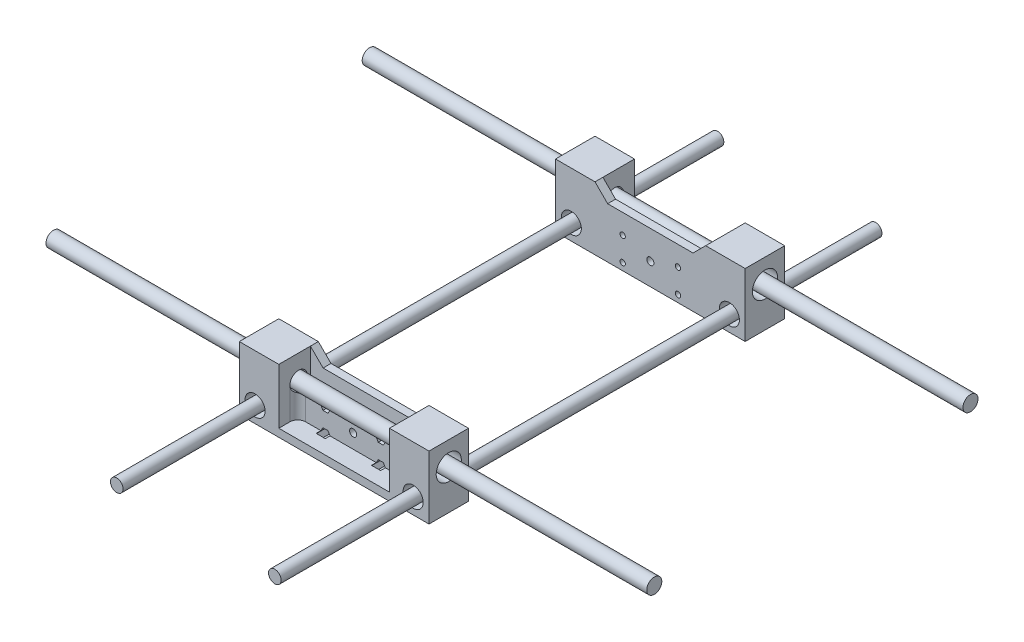
SolidWorks part; units mm, degrees
note: The reader was unsure of these and kept them because the rebuilt part matched: shared geometry of "Sketch3<3>".
ref_plane "Front" through (0, 0, 0) normal (0, 0, 1) x (1, 0, 0)
ref_plane "Top" through (0, 0, 0) normal (0, 1, 0) x (1, 0, 0)
ref_plane "Right" through (0, 0, 0) normal (1, 0, 0) x (0, 0, -1)
sketch "Sketch1" plane through (0, 0, 0) normal (0, 0, 1) x (1, 0, 0)
  line L0 (-50, 0) -> (50, 0) construction
  line L1 (0, 0) -> (0, 10) construction
  line L2 (35, 10) -> (-35, 10)
  line L3 (60, 30) -> (60, -10)
  line L4 (60, -10) -> (-60, -10)
  line L5 (-60, 30) -> (-60, -10)
  line L7 (-60, 30) -> (-35, 30)
  line L8 (-35, 30) -> (-35, 10)
  line L9 (35, 10) -> (35, 30)
  line L10 (35, 30) -> (60, 30)
  circle A0 centre (50, 0) radius 6.35
  circle A1 centre (-50, 0) radius 6.35
  dimension "Sleeve Bearing OD" = 12.7
  dimension "D1" = 100
  dimension "D3" = 120
  dimension "D4" = 20
  dimension "D5" = 20
  dimension "D6" = 25
extrude "Boss-Extrude1" add sketch "Sketch1" along normal mid plane 25
sketch "Sketch3" plane through (-60, 0, 0) normal (-1, 0, 0) x (0, 0, 1)
  line L0 (0, 0) -> (0, 15) construction
  circle A0 centre (0, 15) radius 7.9375
  circle A1 centre (0, 15) radius 5.5
  dimension "D1" = 15.875
  dimension "Sliding Shaft Clearance Hole" = 11
  dimension "D2" = 15
extrude "Cut-Extrude1" cut sketch "Sketch3" against normal blind 12
extrude "Cut-Extrude3" cut sketch "Sketch3<3>" against normal up to surface (95 mm away) contours A1
sketch "Sketch3<3>" plane through (-60, 0, 0) normal (-1, 0, 0) x (0, 0, 1) same geometry as "Sketch3"
mirror "Mirror1" about plane through (0, 0, 0) normal (1, 0, 0) of "Cut-Extrude3", "Cut-Extrude1"
sketch "Sketch4" plane through (0, 0, -12.5) normal (0, 0, -1) x (-1, 0, 0)
  line L0 (60, -10) -> (-60, -10) construction
  line L1 (-35, 10) -> (35, 10)
  line L2 (-35, 10) -> (-35, -10)
  line L3 (-35, -10) -> (35, -10)
  line L4 (35, 10) -> (35, -10)
  line L5 (35, 10) -> (35, 30) construction
  line L6 (-35, 10) -> (35, 10) construction
extrude "Cut-Extrude2" cut sketch "Sketch4" against normal blind 12
sketch "Sketch8" plane through (0, 0, 12.5) normal (0, 0, -1) x (-1, 0, 0)
  line L0 (35, 30) -> (60, 30) construction
  line L1 (-35, 30) -> (-35, -10) construction
  line L2 (-35, 30) -> (-35, -10)
  line L4 (35, -10) -> (35, 30) construction
  line L5 (-35, -10) -> (35, -10)
  line L6 (35, -10) -> (35, 30)
  line L7 (-35, 30) -> (-27, 22)
  line L8 (-27, 22) -> (27, 22)
  line L9 (27, 22) -> (35, 30)
  line L10 (0, 0) -> (0, 22) construction
  line L11 (35, 10) -> (-35, 10) construction
  dimension "D1" = 12
  dimension "D2" = 45
  dimension "D3" = 8
extrude "Boss-Extrude5" add sketch "Sketch8" along normal blind 5
fillet "Fillet4" [suppressed] radius 15
sketch "Sketch10" plane through (0, 0, -0.5) normal (0, 0, -1) x (-1, 0, 0)
  line L0 (-35, -10) -> (35, -10)
extrude "Extrude-Thin1" add sketch "Sketch10" along normal up to surface (12 mm away) thin up to face at (47.5, 10, -12.5) thin type one direction reverse wall 5
fillet "Fillet2" radius 5 2 edges at (35, 2.2614, -0.5) (-35, 2.2614, -0.5)
sketch "Sketch11" plane through (0, 0, 12.5) normal (0, 0, 1) x (1, 0, 0)
  line L0 (0, 2) -> (0, 22) construction
  line L1 (17.5, -5.5) -> (-17.5, -5.5) construction
  line L2 (17.5, -5.5) -> (17.5, 9.5) construction
  line L3 (17.5, 9.5) -> (-17.5, 9.5) construction
  line L4 (-17.5, -5.5) -> (-17.5, 9.5) construction
  line L5 (17.5, -5.5) -> (-17.5, 9.5) construction
  line L6 (17.5, 9.5) -> (-17.5, -5.5) construction
  line L8 (-27, 22) -> (27, 22) construction
  point P0 (0, 2)
  dimension "D1" = 15
  dimension "D2" = 35
  dimension "D3" = 20
hole_wizard "M3 Clearance Hole1" positions "Sketch16" profile "Sketch15" hole size "M3" standard "Ansi Metric"
sketch "Sketch16" plane through (0, 0, 12.5) normal (0, 0, 1) x (1, 0, 0)
  point P0 (-17.5, 9.5)
  point P1 (17.5, 9.5)
  point P4 (17.5, -5.5)
  point P7 (-17.5, -5.5)
sketch "Sketch15" plane through (-17.5, 9.5, 12.5) normal (1, 0, 0) x (0, -1, 0)
  line L0 (0, 0) -> (0, 14.0215)
  line L1 (0, 14.0215) -> (1.7, 13)
  line L2 (1.7, 13) -> (1.7, 0)
  line L5 (1.7, 0) -> (0, 0)
  line L10 (0, 14.0215) -> (-1.7, 13) construction
  line L11 (0, -6.35) -> (0, 107.95) construction
  dimension "Hole Dia." = 3.4
  dimension "Hole Depth" = 13
  dimension "Drill Angle" = 118
sketch "Sketch17" plane through (0, 0, -0.5) normal (0, 0, -1) x (-1, 0, 0)
  line L1 (15.9123, 12.25) -> (14.3246, 9.5)
  line L2 (14.3246, 9.5) -> (15.9123, 6.75)
  line L3 (15.9123, 6.75) -> (19.0877, 6.75)
  line L4 (19.0877, 6.75) -> (20.6754, 9.5)
  line L5 (20.6754, 9.5) -> (19.0877, 12.25)
  line L6 (19.0877, 12.25) -> (15.9123, 12.25)
  line L7 (15.9123, -2.75) -> (14.3246, -5.5)
  line L8 (14.3246, -5.5) -> (15.9123, -8.25)
  line L9 (15.9123, -8.25) -> (19.0877, -8.25)
  line L10 (19.0877, -8.25) -> (20.6754, -5.5)
  line L11 (20.6754, -5.5) -> (19.0877, -2.75)
  line L12 (19.0877, -2.75) -> (15.9123, -2.75)
  line L13 (-19.0877, -2.75) -> (-20.6754, -5.5)
  line L14 (-20.6754, -5.5) -> (-19.0877, -8.25)
  line L15 (-19.0877, -8.25) -> (-15.9123, -8.25)
  line L16 (-15.9123, -8.25) -> (-14.3246, -5.5)
  line L17 (-14.3246, -5.5) -> (-15.9123, -2.75)
  line L18 (-15.9123, -2.75) -> (-19.0877, -2.75)
  line L19 (-19.0877, 12.25) -> (-20.6754, 9.5)
  line L20 (-20.6754, 9.5) -> (-19.0877, 6.75)
  line L21 (-19.0877, 6.75) -> (-15.9123, 6.75)
  line L22 (-15.9123, 6.75) -> (-14.3246, 9.5)
  line L23 (-14.3246, 9.5) -> (-15.9123, 12.25)
  line L24 (-15.9123, 12.25) -> (-19.0877, 12.25)
  circle A0 centre (17.5, 9.5) radius 2.75 construction
  circle A1 centre (17.5, -5.5) radius 2.75 construction
  circle A2 centre (-17.5, -5.5) radius 2.75 construction
  circle A3 centre (-17.5, 9.5) radius 2.75 construction
  dimension "D1" = 5.5
extrude "Cut-Extrude4" cut sketch "Sketch17" against normal blind 8 and the other way blind 3
sketch "Sketch5" plane through (0, 0, 0) normal (1, 0, 0) x (0, 0, -1)
  circle A0 centre (0, 15) radius 4.7625
  dimension "Sliding Shaft Diamter" = 9.525
extrude "Boss-Extrude3" add sketch "Sketch5" along normal mid plane 380 separate body
sketch "Sketch7" plane through (0, 0, 0) normal (0, 0, 1) x (1, 0, 0)
  circle A0 centre (50, 0) radius 4
  circle A1 centre (-50, 0) radius 4
  dimension "D1" = 8
extrude "Boss-Extrude4" add sketch "Sketch7" along normal blind 300 and the other way blind 80 separate body
hole_wizard "M4 Clearance Hole1" positions "Sketch19" profile "Sketch18" hole size "M4" standard "Ansi Metric" end condition through all
sketch "Sketch19" plane through (0, 0, 12.5) normal (0, 0, 1) x (1, 0, 0)
  point P0 (0, 4)
  dimension "D1" = 18
sketch "Sketch18" plane through (0, 4, 12.5) normal (1, 0, 0) x (0, -1, 0)
  line L0 (0, 0) -> (0, 92.5)
  line L1 (0, 92.5) -> (2.25, 92.5)
  line L2 (2.25, 92.5) -> (2.25, 0)
  line L5 (2.25, 0) -> (0, 0)
  line L11 (0, -6.35) -> (0, 107.95) construction
  dimension "Thru Hole Dia." = 4.5
  dimension "Thru Hole Depth" = 92.5
ref_plane "Plane1" through (0, 0, 100) normal (0, 0, 1) x (1, 0, 0)
mirror "Mirror2" about plane through (0, 0, 100) normal (0, 0, 1) of bodies 117 107 106
equation "\"Sliding Shaft Diamter\"=0.375*25.4"
